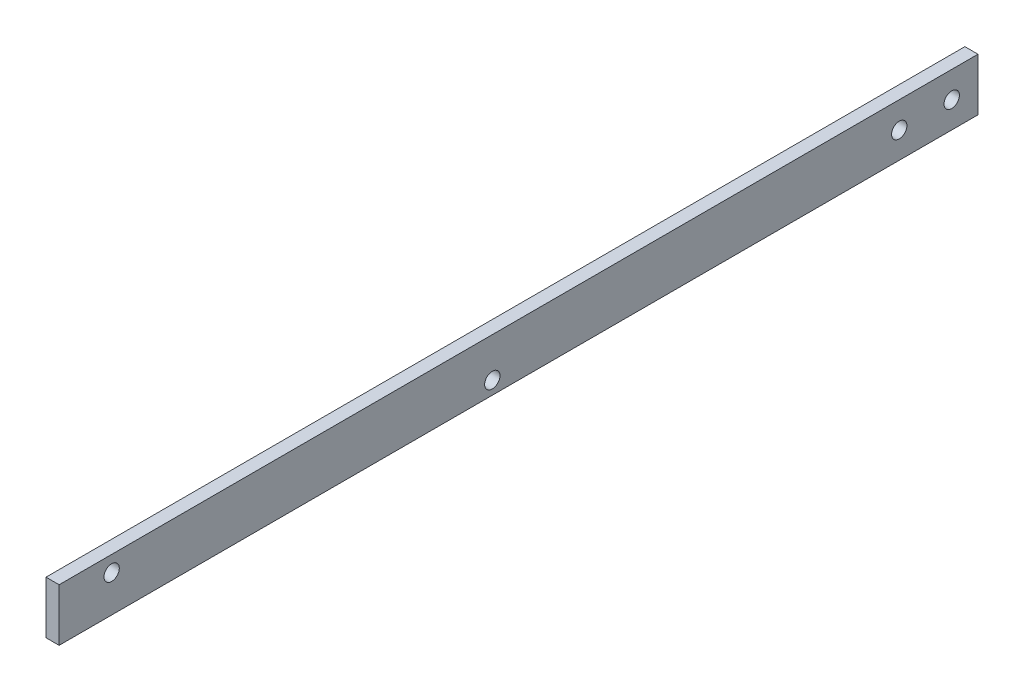
SolidWorks part; units mm, degrees
ref_plane "Front Plane" through (0, 0, 0) normal (0, 0, 1) x (1, 0, 0)
ref_plane "Top Plane" through (0, 0, 0) normal (0, 1, 0) x (1, 0, 0)
ref_plane "Right Plane" through (0, 0, 0) normal (1, 0, 0) x (0, 0, -1)
sketch "Sketch1" plane through (0, 0, 0) normal (0, 0, 1) x (1, 0, 0)
  line L1 (0, 0) -> (3.175, 0)
  line L2 (0, 0) -> (0, -12.7)
  line L3 (0, -12.7) -> (3.175, -12.7)
  line L4 (3.175, 0) -> (3.175, -12.7)
  dimension "D1" = 3.175
  dimension "D2" = 12.7
extrude "Boss-Extrude1" add sketch "Sketch1" along normal blind 222.25
sketch "Sketch2" plane through (3.175, 0, 0) normal (1, 0, 0) x (0, 0, -1)
  line L0 (0, -12.7) -> (0, 0) construction
  line L1 (-222.25, -12.7) -> (-222.25, 0) construction
  line L2 (-117.475, -6.35) -> (-117.475, 0)
  line L3 (-222.25, -12.7) -> (0, -12.7) construction
  line L5 (-222.25, 0) -> (0, 0) construction
  circle A0 centre (-117.475, -9.525) radius 3.175 construction
  point P6 (-209.55, -3.81)
  point P8 (-117.475, -9.525)
  point P10 (-6.35, -6.35)
  point P14 (0, 0)
  point P16 (-9.3127, 0)
  dimension "D3" = 6.35
  dimension "D4" = 104.775
  dimension "D5" = 6.35
  dimension "D1" = 12.7
  dimension "D2" = 3.81
  dimension "D6" = 6.35
  dimension "D7" = 6.35
hole_wizard "#6 (0.146) Diameter Hole1" positions "3DSketch1" profile "Sketch3" hole size "#6" standard "ANSI Inch" end condition through all
sketch3d "3DSketch1"
  point P2 (3.175, -3.81, 209.55)
sketch "Sketch3" plane through (3.175, -3.81, 209.55) normal (0, 1, 0) x (0, 0, -1)
  line L0 (0, 0) -> (0, 3.175)
  line L1 (0, 3.175) -> (1.8542, 3.175)
  line L2 (1.8542, 3.175) -> (1.8542, 0)
  line L5 (1.8542, 0) -> (0, 0)
  line L11 (0, -6.35) -> (0, 107.95) construction
  dimension "Thru Hole Dia." = 3.7084
  dimension "Thru Hole Depth" = 3.175
hole_wizard "#6 (0.146) Diameter Hole2" positions "3DSketch3" profile "Sketch5" hole size "#6" standard "ANSI Inch" end condition through all
sketch3d "3DSketch3"
  point P0 (3.175, -9.525, 117.475)
sketch "Sketch5" plane through (3.175, -9.525, 117.475) normal (0, 1, 0) x (0, 0, -1)
  line L0 (0, 0) -> (0, 3.175)
  line L1 (0, 3.175) -> (1.8542, 3.175)
  line L2 (1.8542, 3.175) -> (1.8542, 0)
  line L5 (1.8542, 0) -> (0, 0)
  line L11 (0, -6.35) -> (0, 107.95) construction
  dimension "Thru Hole Dia." = 3.7084
  dimension "Thru Hole Depth" = 3.175
sketch "Sketch9" plane through (3.175, 0, 0) normal (1, 0, 0) x (0, 0, -1)
  line L0 (0, -12.7) -> (0, 0) construction
  line L1 (-222.25, 0) -> (0, 0) construction
  point P0 (-6.35, -6.35)
  point P5 (-19.05, -6.35)
  dimension "D1" = 6.35
  dimension "D2" = 6.35
  dimension "D3" = 12.7
hole_wizard "#6 (0.146) Diameter Hole3" positions "3DSketch5" profile "Sketch10" hole size "#6" standard "ANSI Inch" end condition through all
sketch3d "3DSketch5"
  point P0 (3.175, -6.35, 6.35)
  point P4 (3.175, -6.35, 19.05)
sketch "Sketch10" plane through (3.175, -6.35, 6.35) normal (0, 1, 0) x (0, 0, -1)
  line L0 (0, 0) -> (0, 3.175)
  line L1 (0, 3.175) -> (1.8542, 3.175)
  line L2 (1.8542, 3.175) -> (1.8542, 0)
  line L5 (1.8542, 0) -> (0, 0)
  line L11 (0, -6.35) -> (0, 107.95) construction
  dimension "Thru Hole Dia." = 3.7084
  dimension "Thru Hole Depth" = 3.175
